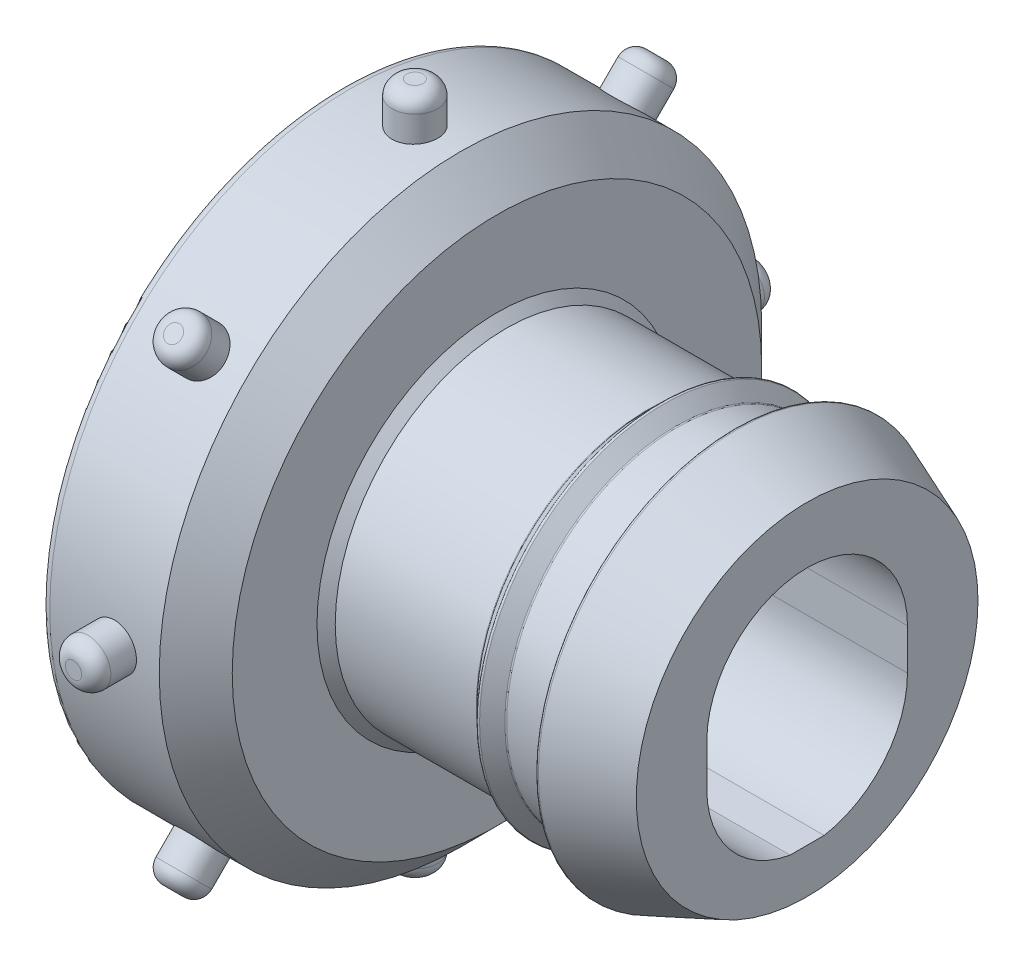
SolidWorks part; units mm, degrees
note: '?' marks a value the reader was unsure of. The reader was unsure of these and kept them because the rebuilt part matched: shared geometry of "Sketch2<3>".
ref_plane "Front Plane" through (0, 0, 0) normal (0, 0, 1) x (1, 0, 0)
ref_plane "Top Plane" through (0, 0, 0) normal (0, 1, 0) x (1, 0, 0)
ref_plane "Right Plane" through (0, 0, 0) normal (1, 0, 0) x (0, 0, -1)
sketch "Sketch1" plane through (0, 0, 0) normal (0, 1, 0) x (1, 0, 0)
  line L0 (0, 0) -> (-17, 0)
  line L1 (0, 0) -> (0, 9.365)
  line L2 (0, 9.365) -> (-3.97, 10.955)
  line L3 (-3.97, 10.955) -> (-3.97, 9.365)
  line L4 (0, 9.365) -> (-19.3321, 9.365) construction
  line L5 (-3.97, 9.365) -> (-7.15, 9.365)
  line L6 (-7.15, 9.365) -> (-7.94, 10.155)
  line L7 (-7.94, 10.155) -> (-8.73, 9.365)
  line L8 (-8.73, 9.365) -> (-17, 9.365)
  line L9 (-17, 9.365) -> (-17, 0)
  dimension "D1" = 17
  dimension "D2" = 9.365
  dimension "D3" = 1.59
  dimension "D4" = 3.97
  dimension "D5" = 7.94
  dimension "D6" = 0.79
revolve "Revolve1" add sketch "Sketch1" angle 360 about L0
sketch "Sketch2" plane through (-17, 0, 0) normal (-1, 0, 0) x (0, 0, 1)
  circle A0 centre (0, 0) radius 9.365
  circle A1 centre (0, 0) radius 9.365 construction
  circle A2 centre (0, 0) radius 6.5
  circle A3 centre (0, 0) radius 16.51
  circle M3 centre (0, 0) radius 9.365
  dimension "D1" = 13
  dimension "D2" = 33.02
extrude "Boss-Extrude1" add sketch "Sketch2" along normal blind 8.5 contours A3 M3 | A2 M3
ref_axis "Axis1" through (-25.5, -18.161, 0) along (0, 1, 0)?
sketch "Sketch4" plane through (-25.5, 0, 0) normal (-1, 0, 0) x (0, 0, 1)
  line L0 (0, -18.161) -> (0, 18.161) construction
  line L1 (9.09, 6.63) -> (-9.09, 6.63)
  line L2 (9.09, 6.63) -> (9.09, -6.92)
  line L3 (9.09, -6.92) -> (-9.09, -6.92)
  line L4 (-9.09, 6.63) -> (-9.09, -6.92)
  circle A1 centre (0, 0) radius 16.51 construction
  point P6 (0, 6.63)
  dimension "D1" = 18.18
  dimension "D2" = 13.55
  dimension "D3" = 6.92
extrude "Cut-Extrude1" cut sketch "Sketch4" against normal blind 7
sketch "Sketch5" plane through (-25.5, 0, 0) normal (-1, 0, 0) x (0, 0, 1)
  circle A0 centre (0, 0) radius 14.14
  dimension "D1" = 28.28
sketch "Sketch6" plane through (0, 0, 0) normal (0, 0, 1) x (1, 0, 0)
  line L0 (-25.5, 14.14) -> (-25.5, -14.14) construction
  circle A0 centre (-25.5, 14.14) radius 0.9
  point P0 (-25.5, 14.14)
  dimension "D1" = 1.8
ref_axis "Axis2" through (-35.0271, 0, 0) along (1, 0, 0)
revolve "Cut-Revolve1" cut sketch "Sketch6" angle 360 about axis through (-35.0271, 0, 0) along (1, 0, 0)
fillet "Fillet1" radius 1 1 edges at (-25.5, 0, -13.24)
ref_plane "Plane1" through (-21.5, 0, 0) normal (-1, 0, 0) x (0, 0, 1)
ref_axis "Axis3" through (-21.5, -18.161, 0) along (0, 1, 0)?
ref_plane "Plane2" through (0, 16.51, 0) normal (0, 1, 0) x (1, 0, 0)
sketch "Sketch7" plane through (0, 16.51, 0) normal (0, 1, 0) x (1, 0, 0)
  circle A0 centre (-21.5, 0) radius 1.25
  dimension "D1" = 2.5
extrude "Boss-Extrude2" add sketch "Sketch7" along normal blind 2.2 and the other way blind 2 contours A0
fillet "Fillet2" radius 0.8 1 edges at (-21.5, 18.71, 1.25)
pattern_circular "CirPattern1" count 8 over 360 about axis through (0, 0, 0) along (1, 0, 0) of "Boss-Extrude2", "Fillet2"
chamfer "Chamfer1" distance 2 angle 45 1 edges at (-17, 0, 16.51)
fillet "Fillet3" radius 0.5 1 edges at (-25.5, 0, 16.51)
fillet "Fillet4" radius 0.1 5 edges at (-8.73, 0, -9.365) (-7.94, 0, -10.155) (-7.15, 0, -9.365) (-3.97, 0, -9.365) (-3.97, 0, -10.955)
chamfer "Chamfer2" distance 0.5 angle 45 1 edges at (-17, 0, 9.365)
extrude "Cut-Extrude2" cut sketch "Sketch2<3>" against normal through all both and the other way through all contours A2
sketch "Sketch2<3>" plane through (-17, 0, 0) normal (-1, 0, 0) x (0, 0, 1) same geometry as "Sketch2"
chamfer "Chamfer3" distance 1 angle 76 1 edges at (-25.5, -6.92, 0)
sketch "Sketch8" plane through (-18.5, 0, 0) normal (-1, 0, 0) x (0, 0, 1)
  line L1 (-9.09, -6.92) -> (-6.5, -6.92)
  line L2 (-9.09, -6.92) -> (-9.09, 0.73)
  line L3 (-9.09, 0.73) -> (-6.5, 0.73)
  line L4 (-6.5, -6.92) -> (-6.5, 0.73)
  circle A0 centre (0, 0) radius 6.5 construction
  dimension "D1" = 7.65
extrude "Boss-Extrude3" add sketch "Sketch8" along normal blind 0.64
fillet "Fillet5" radius 0.5 2 edges at (-19.14, 0.73, -7.795) (-19.14, -3.095, -6.5)
sketch "Sketch9" plane through (0, 0, 0) normal (1, 0, 0) x (0, 0, -1)
  circle A0 centre (0, 0) radius 9.365
  circle A1 centre (0, 0) radius 9.365 construction
extrude "Boss-Extrude4" add sketch "Sketch9" against normal up to surface (18.5 mm away) contours A0 up to face at (-18.5, 0.11, -3.25)
sketch "Sketch10" plane through (-18.5, 0, 0) normal (-1, 0, 0) x (0, 0, 1)
  line L0 (0, 0) -> (50000, 0) construction
  line L1 (0, -18.161) -> (0, 18.161) construction
  line L2 (-5.5, 0.75) -> (-5.5, -1.5)
  line L3 (5.5, 0.75) -> (5.5, -1.5)
  circle A0 centre (0, 0.75) radius 5.5
  circle A1 centre (0, -1.5) radius 5.5
  point P11 (5.5, -1.5)
  line M3 (-6.5, -6.92) -> (9.09, -6.92)
  dimension "D2" = 11
  dimension "D3" = 11
  dimension "D1" = 1.5
  dimension "D4" = 1.5
extrude "Cut-Extrude3" cut sketch "Sketch10" against normal through all contours A0 L0 A1 | A1 L0 | L0 A1 A0 | A0 A1 M3 | L0 A0 A1 L3 | L0 A1 A0 | A0 L0 L3 | L0 L2 A1 A0 | L0 A0 A1 | L2 L0 A0
chamfer "Chamfer4" distance 3 angle 45 5 edges at (-18.5, -5.0433, -4.2066) (-18.5, 6.25, 0) (-18.5, -5.0433, 4.2066) (-18.5, -0.375, -5.5) (-18.5, -0.375, 5.5)
equation "\"WallThick\"= 1.2'thickness of wall for printer"
equation "\"dHole\"= 3.3'diameter of screw hole"
equation "\"D3@Sketch4\"=33.02/2-9.59"
equation "\"D1@Boss-Extrude2\"=(37.42-33.02)/2"
